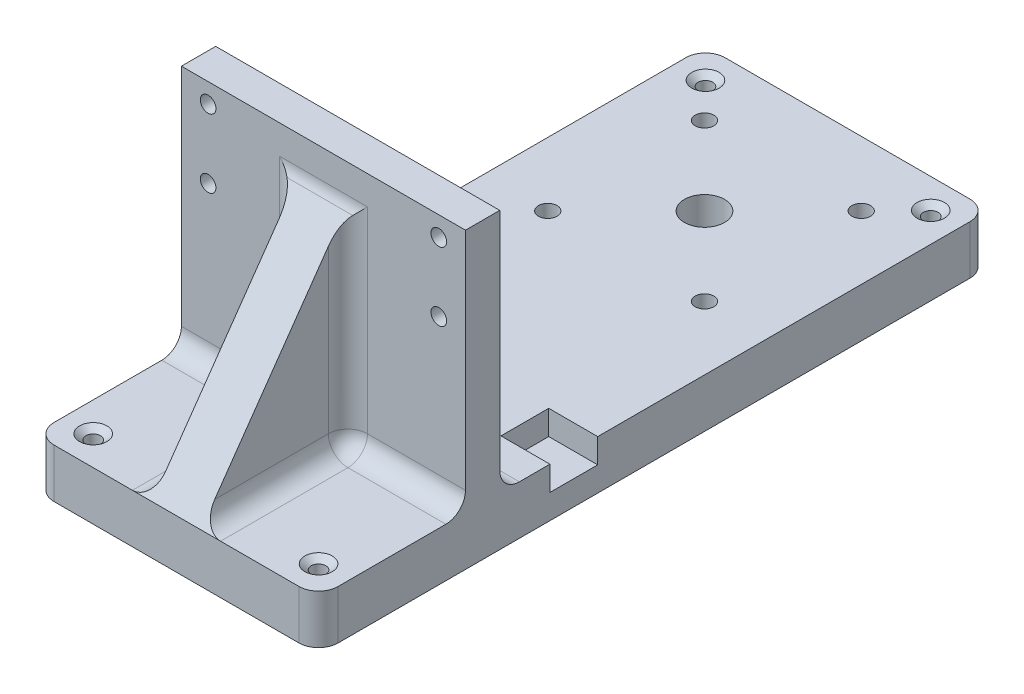
SolidWorks part; units mm, degrees
ref_plane "Front Plane" through (0, 0, 0) normal (0, 0, 1) x (1, 0, 0)
ref_plane "Top Plane" through (0, 0, 0) normal (0, 1, 0) x (1, 0, 0)
ref_plane "Right Plane" through (0, 0, 0) normal (1, 0, 0) x (0, 0, -1)
sketch "Sketch1" plane through (0, 0, 0) normal (0, 0, 1) x (1, 0, 0)
  line L1 (-36.83, 34.925) -> (36.83, 34.925)
  line L2 (-36.83, 34.925) -> (-36.83, -34.925)
  line L3 (-36.83, -34.925) -> (36.83, -34.925)
  line L4 (36.83, 34.925) -> (36.83, -34.925)
  point P4 (0, 34.925)
  point P6 (36.83, 0)
  dimension "D1" = 69.85
  dimension "D2" = 73.66
extrude "Boss-Extrude1" add sketch "Sketch1" along normal blind 8.89
sketch "Sketch2" plane through (0, 0, 0) normal (0, 0, -1) x (-1, 0, 0)
  line L0 (0, 34.925) -> (0, -34.925) construction
  line L1 (-36.83, 34.925) -> (36.83, 34.925) construction
  line L2 (36.83, -34.925) -> (-36.83, -34.925) construction
  circle A0 centre (-29.9085, 29.845) radius 2.032
  circle A1 centre (-29.9085, 12.065) radius 2.032
  circle A2 centre (29.9085, 12.065) radius 2.032
  circle A3 centre (29.9085, 29.845) radius 2.032
  dimension "D1" = 4.064
  dimension "D2" = 4.064
  dimension "D3" = 17.78
  dimension "D4" = 59.817
  dimension "D5" = 5.08
extrude "Cut-Extrude1" cut sketch "Sketch2" against normal up to surface (8.89 mm away) up to face at (0, 0, 8.89)
sketch "Sketch3" plane through (0, 0, 0) normal (0, 0, -1) x (-1, 0, 0)
  line L1 (-36.83, -41.275) -> (36.83, -41.275)
  line L2 (-36.83, -41.275) -> (-36.83, -28.575)
  line L3 (-36.83, -28.575) -> (36.83, -28.575)
  line L4 (36.83, -41.275) -> (36.83, -28.575)
  line L5 (36.83, 34.925) -> (36.83, -34.925) construction
  point P5 (-36.83, -34.925)
  dimension "D2" = 12.7
extrude "Boss-Extrude2" add sketch "Sketch3" along normal blind 127
sketch "Sketch4" plane through (0, 0, 8.89) normal (0, 0, 1) x (1, 0, 0)
  line L0 (-36.83, 34.925) -> (-36.83, -34.925) construction
  line L1 (36.83, -41.275) -> (-36.83, -41.275)
  line L2 (36.83, -41.275) -> (36.83, -28.575)
  line L3 (36.83, -28.575) -> (-36.83, -28.575)
  line L4 (-36.83, -41.275) -> (-36.83, -28.575)
  point P7 (36.83, -34.925)
  dimension "D1" = 12.7
extrude "Boss-Extrude3" add sketch "Sketch4" along normal blind 38.1 and the other way up to surface (8.89 mm away) other way up to face at (0, -38.1, 0)
sketch "Sketch5" plane through (36.83, 0, 0) normal (1, 0, 0) x (0, 0, -1)
  line L2 (-46.99, -28.575) -> (-8.89, -28.575) construction
  line L3 (-46.99, -28.575) -> (-8.89, 25.8374)
  line L4 (-8.89, -28.575) -> (-8.89, 34.925) construction
  line L6 (-46.99, -28.575) -> (-8.89, -28.575)
  line L7 (-8.89, -28.575) -> (-8.89, 25.8374)
  dimension "D1" = 35
extrude "Boss-Extrude4" add sketch "Sketch5" against normal mid plane 12.7 from offset 36.83 offset against normal yes
sketch "Sketch6" plane through (0, 0, 0) normal (0, 0, -1) x (-1, 0, 0)
  line L0 (0, 34.925) -> (0, -28.575) construction
  line L1 (-36.83, 34.925) -> (36.83, 34.925) construction
  line L2 (36.83, -28.575) -> (-36.83, -28.575) construction
sketch "Sketch7" plane through (0, -28.575, 0) normal (0, 1, 0) x (1, 0, 0)
  line L1 (-36.83, 0) -> (36.83, 0) construction
  line L2 (-20.32, 69.596) -> (-20.32, 110.236) construction
  line L3 (20.32, 69.596) -> (-20.32, 69.596) construction
  circle A0 centre (0, 26.416) radius 2.667
  circle A1 centre (0, 89.916) radius 5.207
  circle A2 centre (-20.32, 69.596) radius 2.413
  circle A3 centre (20.32, 69.596) radius 2.413
  circle A4 centre (20.32, 110.236) radius 2.413
  circle A5 centre (-20.32, 110.236) radius 2.413
  point P15 (0, 69.596)
  point P16 (-20.32, 89.916)
  dimension "D1" = 5.334
  dimension "D2" = 10.414
  dimension "D7" = 4.826
  dimension "D3" = 63.5
  dimension "D4" = 26.416
  dimension "D5" = 40.64
  dimension "D6" = 40.64
extrude "Cut-Extrude2" cut sketch "Sketch7" against normal blind 12.7
sketch "Sketch27" plane through (-36.83, 0, 0) normal (-1, 0, 0) x (0, 0, 1)
  line L0 (-127, -28.575) -> (0, -28.575) construction
  line L1 (-25.4, -28.575) -> (-13.0048, -28.575)
  line L2 (-25.4, -28.575) -> (-25.4, -34.925)
  line L3 (-25.4, -34.925) -> (-13.0048, -34.925)
  line L4 (-13.0048, -28.575) -> (-13.0048, -34.925)
  line L5 (8.89, -34.925) -> (0, -34.925) construction
  line L6 (0, 34.925) -> (0, -28.575) construction
  dimension "D1" = 12.3952
  dimension "D2" = 25.4
extrude "Cut-Extrude3" cut sketch "Sketch27" against normal blind 12.7
sketch "Sketch28" plane through (36.83, 0, 0) normal (1, 0, 0) x (0, 0, -1)
  line L0 (127, -28.575) -> (0, -28.575) construction
  line L1 (25.4, -28.575) -> (13.0048, -28.575)
  line L2 (25.4, -28.575) -> (25.4, -34.925)
  line L3 (25.4, -34.925) -> (13.0048, -34.925)
  line L4 (13.0048, -28.575) -> (13.0048, -34.925)
  line L5 (-8.89, -34.925) -> (0, -34.925) construction
  dimension "D1" = 12.3952
  dimension "D2" = 25.4
extrude "Cut-Extrude4" cut sketch "Sketch28" against normal blind 12.7
hole_wizard "CSK for #6 Flat Head Machine Screw (100)1" positions "Sketch31" profile "Sketch32" countersink size "#6" standard "ANSI Inch" end condition up to next
sketch "Sketch31" plane through (0, -28.575, 0) normal (0, 1, 0) x (1, 0, 0)
  line L0 (-36.83, 127) -> (-36.83, 25.4) construction
  line L1 (36.83, 127) -> (36.83, 25.4) construction
  line L2 (-36.83, 127) -> (36.83, 127) construction
  line L4 (-6.35, -46.99) -> (-36.83, -46.99) construction
  point P0 (-29.21, -39.37)
  point P2 (29.21, -39.37)
  point P4 (29.21, 119.38)
  point P6 (-29.21, 119.38)
  dimension "D1" = 7.62
  dimension "D2" = 7.62
  dimension "D3" = 7.62
  dimension "D4" = 7.62
sketch "Sketch32" plane through (-29.21, -28.575, 39.37) normal (1, 0, 0) x (0, 0, 1)
  line L0 (0, 0) -> (0, 12.7)
  line L1 (0, 12.7) -> (1.8986, 12.7)
  line L2 (1.8986, 12.7) -> (1.8986, 1.38)
  line L3 (1.8986, 1.38) -> (3.5433, 0)
  line L5 (3.5433, 0) -> (0, 0)
  line L6 (-1.8986, 1.38) -> (-3.5433, 0) construction
  line L11 (0, -6.35) -> (0, 107.95) construction
  dimension "Thru Hole Dia." = 3.7973
  dimension "Thru Hole Depth" = 12.7
  dimension "Near C'Sink Dia." = 7.0866
  dimension "Near C'Sink Angle" = 100
fillet "Fillet1" radius 5.08 12 edges at (36.83, -34.925, -127) (-36.83, -34.925, -127) (-36.83, -34.925, 46.99) (36.83, -34.925, 46.99) (6.35, -28.575, 27.94) (-6.35, -28.575, 27.94) (-21.59, -28.575, 8.89) (21.59, -28.575, 8.89) (0, -28.575, 0) (0, 25.8374, 8.89) (6.35, -1.3688, 8.89) (-6.35, -1.3688, 8.89)
sketch "Sketch35" plane through (0, -41.275, 0) normal (0, -1, 0) x (1, 0, 0)
  circle A0 centre (20.32, -110.236) radius 5.08
  circle A1 centre (-20.32, -110.236) radius 5.08
  circle A2 centre (-20.32, -69.596) radius 5.08
  circle A3 centre (20.32, -69.596) radius 5.08
  dimension "D1" = 10.16
extrude "Cut-Extrude5" cut sketch "Sketch35" against normal blind 6.35
